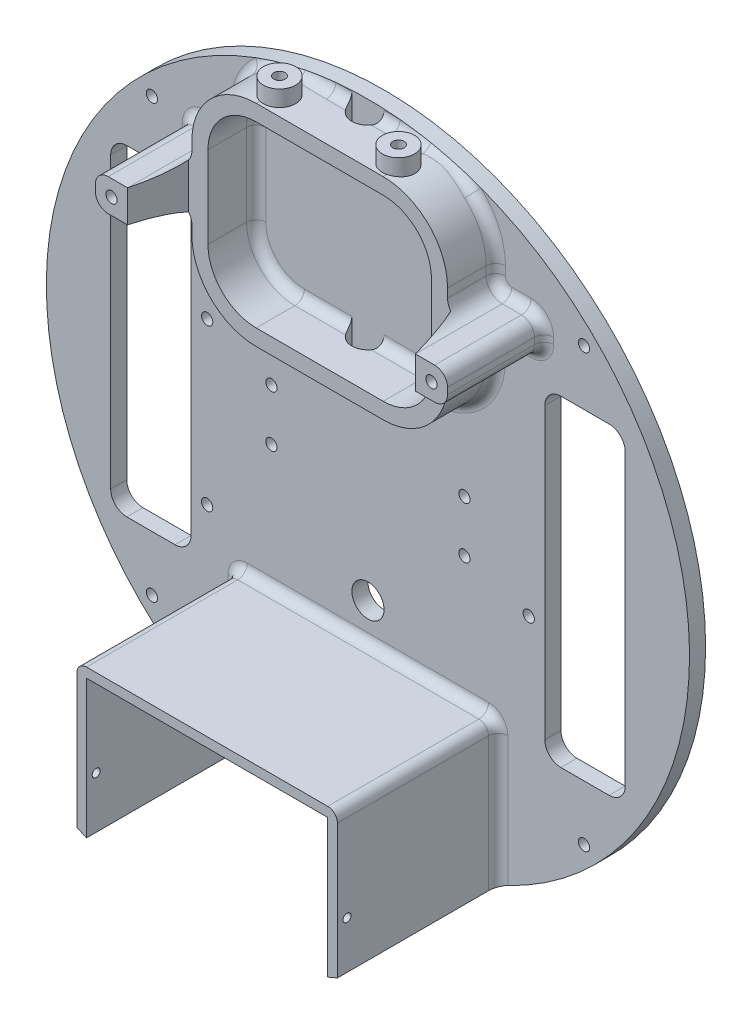
SolidWorks part; units mm, degrees
ref_plane "Płaszczyzna przednia" through (0, 0, 0) normal (0, 0, 1) x (1, 0, 0)
ref_plane "Płaszczyzna górna" through (0, 0, 0) normal (0, 1, 0) x (1, 0, 0)
ref_plane "Płaszczyzna prawa" through (0, 0, 0) normal (1, 0, 0) x (0, 0, -1)
sketch "Szkic1" plane through (0, 0, 0) normal (0, 0, 1) x (1, 0, 0)
  circle A0 centre (0, 0) radius 100
  dimension "D1" = 200
extrude "Dodanie-wyciągnięcie1" add sketch "Szkic1" along normal blind 5
sketch "Szkic2" plane through (0, 0, 5) normal (0, 0, 1) x (1, 0, 0)
  line L0 (-100, 0) -> (100, 0) construction
  line L1 (-30, 10) -> (30, 10) construction
  line L2 (-30, 10) -> (-30, -60) construction
  line L3 (-30, -60) -> (30, -60) construction
  line L4 (30, 10) -> (30, -60) construction
  line L5 (-80, 50) -> (-55, 50)
  line L6 (-80, 50) -> (-80, -50)
  line L7 (-80, -50) -> (-55, -50)
  line L8 (-55, 50) -> (-55, -50)
  line L9 (55, 50) -> (80, 50)
  line L10 (55, 50) -> (55, -50)
  line L11 (55, -50) -> (80, -50)
  line L12 (80, 50) -> (80, -50)
  circle A0 centre (-30, -8) radius 1.75
  circle A1 centre (30, -8) radius 1.75
  circle A2 centre (0, 0) radius 100 construction
  circle A3 centre (-30, 8) radius 1.75
  circle A4 centre (30, 8) radius 1.75
  dimension "D13" = 3.5
  dimension "D14" = 3.5
  dimension "D17" = 3.5
  dimension "D18" = 3.5
  dimension "D1" = 70
  dimension "D2" = 60
  dimension "D3" = 30
  dimension "D4" = 100
  dimension "D5" = 100
  dimension "D6" = 50
  dimension "D7" = 50
  dimension "D8" = 25
  dimension "D9" = 25
  dimension "D10" = 25
  dimension "D11" = 25
  dimension "D12" = 10
  dimension "D15" = 18
  dimension "D16" = 18
  dimension "D19" = 8
  dimension "D20" = 8
sketch "Szkic4" plane through (0, 0, 5) normal (0, 0, 1) x (1, 0, 0)
  line L0 (-30, -60) -> (30, -60) construction
  line L1 (-35, -70) -> (35, -70)
  line L2 (-35, -70) -> (-35, -90)
  line L3 (-35, -90) -> (35, -90)
  line L4 (35, -70) -> (35, -90)
  line L6 (-37, -68) -> (37, -68)
  line L7 (-37, -68) -> (-37, -92)
  line L8 (-37, -92) -> (37, -92)
  line L9 (37, -68) -> (37, -92)
  dimension "D1" = 20
  dimension "D2" = 70
  dimension "D3" = 10
  dimension "D4" = 35
  dimension "D5" = 24
  dimension "D6" = 74
  dimension "D7" = 2
  dimension "D8" = 2
extrude "Dodanie-wyciągnięcie3" add sketch "Szkic4" along normal blind 40
sketch "Szkic6" plane through (0, -68, 0) normal (0, 1, 0) x (1, 0, 0)
  line L1 (30, -80) -> (23, -80)
  line L2 (30, -80) -> (30, -73)
  line L3 (30, -73) -> (23, -73)
  line L4 (23, -80) -> (23, -73)
  line L5 (37, -5) -> (-37, -5) construction
  line L6 (-19, -80) -> (-26, -80)
  line L7 (-19, -80) -> (-19, -73)
  line L8 (-19, -73) -> (-26, -73)
  line L9 (-26, -80) -> (-26, -73)
  line L10 (30, -22) -> (23, -22)
  line L11 (30, -22) -> (30, -15)
  line L12 (30, -15) -> (23, -15)
  line L13 (23, -22) -> (23, -15)
  line L14 (-19, -22) -> (-26, -22)
  line L15 (-19, -22) -> (-19, -15)
  line L16 (-19, -15) -> (-26, -15)
  line L17 (-26, -22) -> (-26, -15)
  line L18 (30, -100) -> (-26, -100)
  line L19 (30, -100) -> (30, -15)
  line L20 (30, -15) -> (-26, -15)
  line L21 (-26, -100) -> (-26, -15)
  line L22 (37, -45) -> (37, -5) construction
  circle A0 centre (26.5, -18.5) radius 1.5
  circle A1 centre (-22.5, -18.5) radius 1.5
  circle A2 centre (26.5, -76.5) radius 1.5
  circle A3 centre (-22.5, -76.5) radius 1.5
  point P4 (23, -18.5)
  point P5 (26.5, -22)
  point P26 (2, -15)
  point P27 (-22.5, -22)
  point P28 (-19, -18.5)
  point P29 (30, -76.5)
  point P30 (-26, -76.5)
  point P31 (-22.5, -80)
  point P32 (26.5, -80)
  dimension "D21" = 3
  dimension "D22" = 3
  dimension "D23" = 3
  dimension "D24" = 3
  dimension "D1" = 7
  dimension "D2" = 7
  dimension "D3" = 7
  dimension "D4" = 7
  dimension "D5" = 7
  dimension "D6" = 7
  dimension "D7" = 7
  dimension "D8" = 7
  dimension "D9" = 85
  dimension "D10" = 56
  dimension "D11" = 10
  dimension "D12" = 35
  dimension "D13" = 3.5
  dimension "D14" = 3.5
  dimension "D15" = 3.5
  dimension "D16" = 3.5
  dimension "D17" = 58
  dimension "D18" = 58
  dimension "D19" = 3.5
  dimension "D20" = 3.5
  dimension "D25" = 3.5
  dimension "D26" = 3.5
  dimension "D27" = 3.5
  dimension "D28" = 3.5
  dimension "D29" = 3.5
  dimension "D30" = 3.5
  dimension "D31" = 3.5
  dimension "D32" = 3.5
extrude "Dodanie-wyciągnięcie4" add sketch "Szkic6" along normal blind 4 contours L4 L1 L2 L3 A2 | L9 L6 L7 L8 A3 | L17 L14 L15 L16 A1 | L13 L10 L11 L12 A0 region at (26.5, -68, 79.901) region at (26.5, -68, 21.901) region at (-25.901, -68, 76.5) region at (-19.099, -68, 18.5)
sketch "Szkic7" plane through (0, 0, 45) normal (0, 0, 1) x (1, 0, 0)
  line L0 (37, -92) -> (37, -68) construction
  line L1 (-37, -68) -> (37, -68)
  line L2 (-37, -68) -> (-37, -70)
  line L3 (-37, -70) -> (37, -70)
  line L4 (37, -68) -> (37, -70)
  dimension "D1" = 2
extrude "Dodanie-wyciągnięcie5" add sketch "Szkic7" along normal blind 46
extrude "Wytnij-wyciągnięcie4" cut sketch "Szkic2" against normal through all
fillet "Zaokrąglenie1" radius 5 8 edges at (-55, 50, 2.5) (-80, 50, 2.5) (-80, -50, 2.5) (-55, -50, 2.5) (80, -50, 2.5) (80, 50, 2.5) (55, -50, 2.5) (55, 50, 2.5)
sketch "Szkic9" plane through (0, 0, 5) normal (0, 0, 1) x (1, 0, 0)
  line L0 (-100, 0) -> (100, 0) construction
  line L1 (-19.75, 96.5) -> (19.75, 96.5)
  line L2 (-39.75, 76.5) -> (-39.75, 51)
  line L3 (-19.75, 31) -> (19.75, 31)
  line L4 (39.75, 76.5) -> (39.75, 51)
  line L5 (-39.75, 96.5) -> (39.75, 31) construction
  line L6 (-39.75, 31) -> (39.75, 96.5) construction
  arc A0 (-39.75, 51) -> (-19.75, 31) centre (-19.75, 51) ccw
  arc A1 (19.75, 31) -> (39.75, 51) centre (19.75, 51) ccw
  arc A2 (19.75, 96.5) -> (39.75, 76.5) centre (19.75, 76.5) cw
  arc A3 (-19.75, 96.5) -> (-39.75, 76.5) centre (-19.75, 76.5) ccw
  point P0 (0, 0)
  point P10 (0, 63.75)
  dimension "D4" = 20
  dimension "D1" = 65.5
  dimension "D2" = 79.5
  dimension "D3" = 31
extrude "Dodanie-wyciągnięcie9" add sketch "Szkic9" along normal blind 15 contours A3 L2 A0 L3 A1 L4 A2 L1
sketch "Szkic10" plane through (0, 0, 20) normal (0, 0, 1) x (1, 0, 0)
  line L8 (19.75, 91.5) -> (-19.75, 91.5)
  line L9 (-34.75, 76.5) -> (-34.75, 51)
  line L10 (-19.75, 36) -> (19.75, 36)
  line L11 (34.75, 51) -> (34.75, 76.5)
  line L12 (19.75, 91.5) -> (-19.75, 91.5)
  line L13 (-34.75, 76.5) -> (-34.75, 51)
  line L14 (-19.75, 36) -> (19.75, 36)
  line L15 (34.75, 51) -> (34.75, 76.5)
  arc A8 (-19.75, 91.5) -> (-34.75, 76.5) centre (-19.75, 76.5) ccw
  arc A9 (-34.75, 51) -> (-19.75, 36) centre (-19.75, 51) ccw
  arc A10 (19.75, 36) -> (34.75, 51) centre (19.75, 51) ccw
  arc A11 (34.75, 76.5) -> (19.75, 91.5) centre (19.75, 76.5) ccw
  arc A12 (-19.75, 91.5) -> (-34.75, 76.5) centre (-19.75, 76.5) ccw
  arc A13 (-34.75, 51) -> (-19.75, 36) centre (-19.75, 51) ccw
  arc A14 (19.75, 36) -> (34.75, 51) centre (19.75, 51) ccw
  arc A15 (34.75, 76.5) -> (19.75, 91.5) centre (19.75, 76.5) ccw
  dimension "D1" = 5
extrude "Wytnij-wyciągnięcie7" cut sketch "Szkic10" against normal blind 15 contours A14 L15 A15 L12 A12 L13 A13 L14
sketch "Szkic18" plane through (0, 0, 5) normal (0, 0, 1) x (1, 0, 0)
  line L0 (50.4153, 63.75) -> (-52.756, 63.75) construction
  line L1 (0, 96.5) -> (0, 31) construction
  line L2 (-39.75, 58.75) -> (-50.75, 58.75)
  line L3 (-39.75, 58.75) -> (-39.75, 68.75)
  line L4 (-39.75, 68.75) -> (-50.75, 68.75)
  line L5 (-54.75, 62.75) -> (-54.75, 64.75)
  line L6 (-39.75, 58.75) -> (-54.75, 68.75) construction
  line L7 (-39.75, 68.75) -> (-54.75, 58.75) construction
  line L8 (-19.75, 96.5) -> (19.75, 96.5) construction
  line L9 (-19.75, 31) -> (19.75, 31) construction
  line L10 (-39.75, 76.5) -> (-39.75, 51) construction
  line L11 (54.75, 62.75) -> (54.75, 64.75)
  line L12 (39.75, 68.75) -> (50.75, 68.75)
  line L13 (39.75, 58.75) -> (39.75, 68.75)
  line L14 (39.75, 58.75) -> (50.75, 58.75)
  arc A0 (-50.75, 58.75) -> (-54.75, 62.75) centre (-50.75, 62.75) cw
  arc A1 (-50.75, 68.75) -> (-54.75, 64.75) centre (-50.75, 64.75) ccw
  arc A2 (50.75, 58.75) -> (54.75, 62.75) centre (50.75, 62.75) ccw
  arc A3 (50.75, 68.75) -> (54.75, 64.75) centre (50.75, 64.75) cw
  point P2 (-47.25, 63.75)
  point P22 (0, 63.75)
  dimension "D3" = 4
  dimension "D4" = 4
  dimension "D1" = 15
  dimension "D2" = 10
extrude "Dodanie-wyciągnięcie16" add sketch "Szkic18" along normal blind 30
sketch "Szkic19" plane through (0, 68.75, 0) normal (0, 1, 0) x (1, 0, 0)
  line L0 (-39.75, -20) -> (-40.75, -20)
  line L1 (-40.75, -20) -> (-44.75, -35)
  line L2 (-39.75, -35) -> (-50.75, -35) construction
  line L3 (-44.75, -35) -> (-44.75, -36)
  line L4 (-44.75, -36) -> (-38.75, -36)
  line L5 (-38.75, -36) -> (-38.75, -20)
  line L6 (-39.75, -20) -> (-19.75, -20) construction
  line L7 (-38.75, -20) -> (-39.75, -20)
  line L9 (-39.75, -35) -> (-39.75, -20) construction
  line L10 (0, 0) -> (0, -48.9855) construction
  line L11 (44.75, -35) -> (44.75, -36)
  line L12 (38.75, -20) -> (39.75, -20)
  line L13 (39.75, -20) -> (40.75, -20)
  line L14 (40.75, -20) -> (44.75, -35)
  line L15 (44.75, -36) -> (38.75, -36)
  line L16 (38.75, -36) -> (38.75, -20)
  dimension "D1" = 1
  dimension "D2" = 5
  dimension "D3" = 1
  dimension "D4" = 1
extrude "Wytnij-wyciągnięcie8" cut sketch "Szkic19" against normal up to surface (10 mm away) up to face at (-44.15, 58.75, 20)
sketch "Szkic20" plane through (0, 0, 35) normal (0, 0, 1) x (1, 0, 0)
  line L0 (0, 0) -> (0, 84.9972) construction
  line L1 (54.75, 63.75) -> (-54.75, 63.75) construction
  line L2 (54.75, 62.75) -> (54.75, 64.75) construction
  line L3 (-54.75, 64.75) -> (-54.75, 62.75) construction
  line L4 (44.75, 58.75) -> (44.75, 68.75) construction
  line L5 (-44.75, 58.75) -> (-44.75, 68.75) construction
  circle A0 centre (-49.75, 63.75) radius 1.75
  circle A1 centre (49.75, 63.75) radius 1.75
  dimension "D1" = 3.5
  dimension "D2" = 3.5
  dimension "D3" = 5
  dimension "D4" = 5
extrude "Wytnij-wyciągnięcie9" cut sketch "Szkic20" against normal up to surface (35 mm away) up to face at (-67.5, 0, 0)
sketch "Szkic21" plane through (0, 0, 0) normal (0, 0, -1) x (-1, 0, 0)
  circle A0 centre (-49.75, 63.75) radius 3.5
  circle A1 centre (49.75, 63.75) radius 3.5
  dimension "D1" = 7
  dimension "D2" = 7
extrude "Wytnij-wyciągnięcie10" cut sketch "Szkic21" against normal blind 30
fillet "Zaokrąglenie3" radius 5 4 edges at (39.75, 58.75, 12.5) (-39.75, 58.75, 12.5) (-39.75, 68.75, 12.5) (39.75, 68.75, 12.5)
sketch "Szkic23" plane through (0, 96.5, 0) normal (0, 1, 0) x (1, 0, 0)
  line L0 (0, 8.4144) -> (0, -36.1193) construction
  line L1 (-100, -5) -> (100, -5) construction
  line L2 (-19.75, -5) -> (19.75, -5) construction
  line L3 (5, -5) -> (-5, -5)
  arc A0 (-5, -5) -> (5, -5) centre (0, -5) ccw
  dimension "D1" = 5
extrude "Wytnij-wyciągnięcie12" cut sketch "Szkic23" against normal up to surface (65.5 mm away) up to face at (0, 31, 12.5)
fillet "Zaokrąglenie4" radius 3 36 edges at (-12.375, 91.5, 5) (-30.3566, 87.1066, 5) (-34.75, 63.75, 5) (-12.375, 36, 5) (12.375, 36, 5) (12.375, 91.5, 5) (30.3566, 87.1066, 5) (34.75, 63.75, 5) (12.375, 31, 5) (33.8921, 36.8579, 5) (39.75, 52.375, 5) (41.2145, 57.2855, 5) (47.75, 58.75, 5) (53.5784, 59.9216, 5) (54.75, 63.75, 5) (53.5784, 67.5784, 5) (47.75, 68.75, 5) (41.2145, 70.2145, 5) (39.75, 75.125, 5) (33.8921, 90.6421, 5) (-12.375, 96.5, 5) (-12.375, 31, 5) (-33.8921, 36.8579, 5) (-39.75, 52.375, 5) (-41.2145, 57.2855, 5) (-47.75, 58.75, 5) (-53.5784, 59.9216, 5) (-54.75, 63.75, 5) (-53.5784, 67.5784, 5) (-47.75, 68.75, 5) (-41.2145, 70.2145, 5) (-39.75, 75.125, 5) (-30.3566, 40.3934, 5) (30.3566, 40.3934, 5) (12.375, 96.5, 5) (-33.8921, 90.6421, 5)
sketch "Szkic24" plane through (0, 0, 5) normal (0, 0, 1) x (1, 0, 0)
  line L0 (-35, -90) -> (35, -90) construction
  line L1 (42.1124, -119.2639) -> (-42.1124, -119.2639)
  line L2 (42.1124, -119.2639) -> (42.1124, -60.7361)
  line L3 (42.1124, -60.7361) -> (-42.1124, -60.7361)
  line L4 (-42.1124, -119.2639) -> (-42.1124, -60.7361)
  line L5 (42.1124, -119.2639) -> (-42.1124, -60.7361) construction
  line L6 (42.1124, -60.7361) -> (-42.1124, -119.2639) construction
  point P0 (0, -90)
extrude "Wytnij-wyciągnięcie13" cut sketch "Szkic24" along normal up to surface (86 mm away) up to face at (0, -69, 91)
sketch "Szkic25" plane through (0, 0, 5) normal (0, 0, 1) x (1, 0, 0)
  line L0 (0, 0) -> (0, -105.8501) construction
  line L1 (-40.5, -46.7025) -> (-40.5, -91.4317)
  line L3 (37.5, -92.7025) -> (37.5, -49.7025)
  line L4 (37.5, -49.7025) -> (-37.5, -49.7025)
  line L5 (-37.5, -92.7025) -> (-37.5, -49.7025)
  line L6 (37.5, -92.7025) -> (-37.5, -49.7025) construction
  line L7 (37.5, -49.7025) -> (-37.5, -92.7025) construction
  line L8 (40.5, -46.7025) -> (-40.5, -46.7025)
  line L9 (40.5, -46.7025) -> (40.5, -91.4317)
  line L10 (40.5, -92.7025) -> (40.5, -46.7025) construction
  line L11 (-40.5, -92.7025) -> (-40.5, -46.7025) construction
  line L12 (-40.5, -91.4317) -> (-37.5, -92.7025)
  line L13 (40.5, -91.4317) -> (37.5, -92.7025)
  circle A0 centre (0, 0) radius 100 construction
  point P3 (0, -71.2025)
  dimension "D1" = 75
  dimension "D2" = 43
  dimension "D3" = 3
extrude "Dodanie-wyciągnięcie17" add sketch "Szkic25" along normal blind 50 contours L5 L4 L3 L13 L9 L8 L1 L12
fillet "Zaokrąglenie5" radius 3 5 edges at (-40.5, -46.7025, 30) (40.5, -46.7025, 30) (0, -46.7025, 5) (40.5, -69.0671, 5) (-40.5, -69.0671, 5)
sketch "Szkic26" plane through (-40.5, 0, 0) normal (-1, 0, 0) x (0, 0, 1)
  line L0 (52, -32.3617) -> (52, -116.8366) construction
  line L1 (55, -49.7025) -> (55, -91.4317) construction
  line L2 (8, -46.7025) -> (55, -46.7025) construction
  circle A0 centre (52, -76.7025) radius 1.25
  dimension "D2" = 2.5
  dimension "D1" = 3
  dimension "D3" = 30
extrude "Wytnij-wyciągnięcie14" cut sketch "Szkic26" against normal up to surface (81 mm away) up to face at (40.5, -70.5671, 31.5)
sketch "Szkic28" plane through (0, 0, 0) normal (0, 0, -1) x (-1, 0, 0)
  circle A0 centre (50, 15.7975) radius 1.75
  circle A1 centre (50, -34.2025) radius 1.75
  circle A2 centre (-50, -14.2025) radius 1.75
extrude "Wytnij-wyciągnięcie16" cut sketch "Szkic28" against normal up to surface (5 mm away) up to face at (0, 49.3967, 5)
sketch "Szkic29" plane through (0, 96.5, 0) normal (0, 1, 0) x (1, 0, 0)
  line L0 (0, 0) -> (0, -34.399) construction
  line L1 (60.0888, -14) -> (-62.4133, -14) construction
  line L2 (-19.75, -20) -> (19.75, -20) construction
  circle A0 centre (-18.5, -14) radius 5
  circle A1 centre (18.5, -14) radius 5
  dimension "D4" = 10
  dimension "D5" = 10
  dimension "D1" = 6
  dimension "D2" = 18.5
  dimension "D3" = 18.5
extrude "Dodanie-wyciągnięcie19" add sketch "Szkic29" against normal blind 2
sketch "Szkic30" plane through (0, 96.5, 0) normal (0, 1, 0) x (1, 0, 0)
  circle A0 centre (18.5, -14) radius 5
  circle A1 centre (-18.5, -14) radius 5
  dimension "D1" = 10
  dimension "D2" = 10
extrude "Dodanie-wyciągnięcie20" add sketch "Szkic30" along normal blind 5
sketch "Szkic31" plane through (0, 101.5, 0) normal (0, 1, 0) x (1, 0, 0)
  circle A0 centre (18.5, -14) radius 1.75
  circle A1 centre (-18.5, -14) radius 1.75
  dimension "D1" = 3.5
  dimension "D2" = 3.5
extrude "Wytnij-wyciągnięcie18" cut sketch "Szkic31" against normal blind 12
sketch "Szkic32" plane through (0, 0, 5) normal (0, 0, 1) x (1, 0, 0)
  line L0 (0, -110.3957) -> (0, 119.5894) construction
  line L1 (144.668, 0) -> (-133.4023, 0) construction
  line L2 (99.5724, 99.5724) -> (-110.7961, -110.7961) construction
  line L3 (117.1037, -117.1037) -> (-113.7314, 113.7314) construction
  circle A0 centre (-67.1751, 67.1751) radius 1.75
  circle A1 centre (-67.1751, -67.1751) radius 1.75
  circle A2 centre (67.1751, -67.1751) radius 1.75
  circle A3 centre (67.1751, 67.1751) radius 1.75
  circle A7 centre (0, -35) radius 5
  point P9 (0, 0)
  dimension "D3" = 3.5
  dimension "D4" = 3.5
  dimension "D5" = 3.5
  dimension "D6" = 3.5
  dimension "D11" = 10
  dimension "D1" = 45
  dimension "D2" = 45
  dimension "D7" = 95
  dimension "D8" = 95
  dimension "D9" = 95
  dimension "D10" = 95
  dimension "D12" = 35
extrude "Wytnij-wyciągnięcie19" cut sketch "Szkic32" against normal up to surface (5 mm away) up to face at (-51.75, 15.7975, 0)
